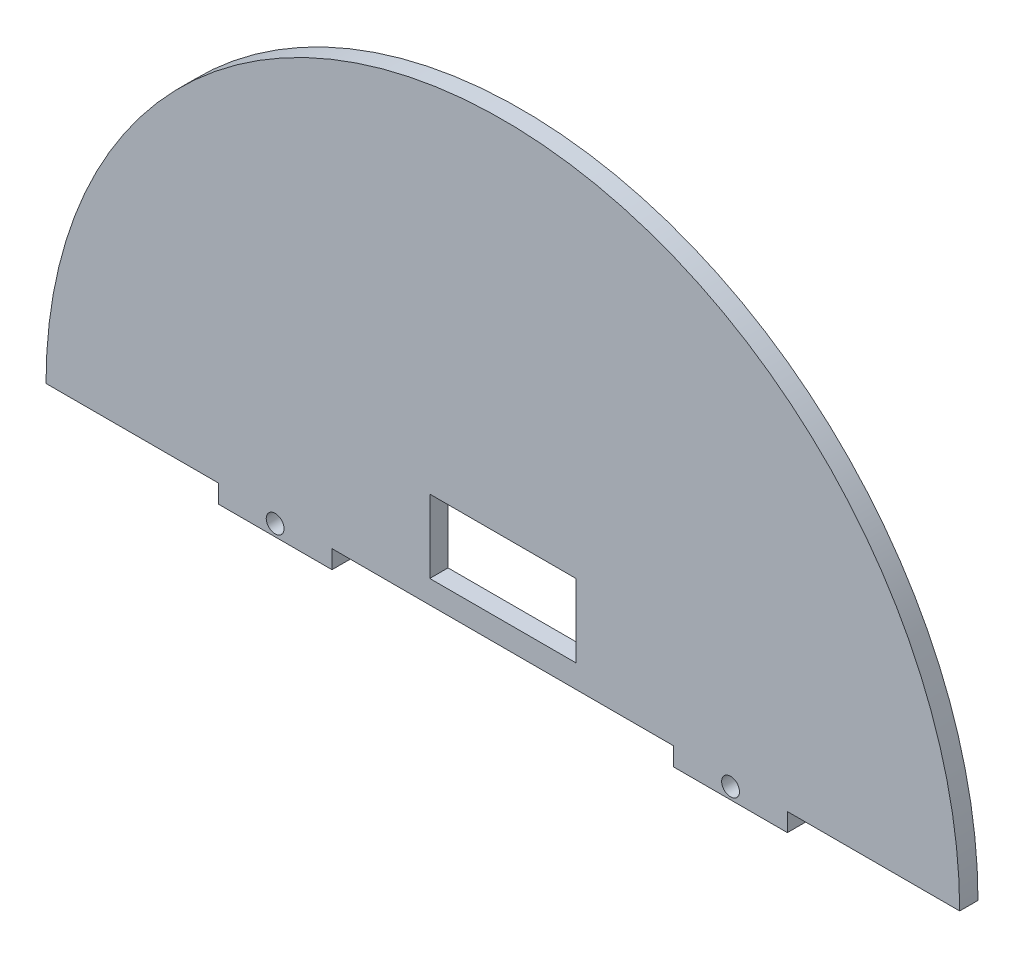
SolidWorks part; units mm, degrees
ref_plane "Front Plane" through (0, 0, 0) normal (0, 0, 1) x (1, 0, 0)
ref_plane "Top Plane" through (0, 0, 0) normal (0, 1, 0) x (1, 0, 0)
ref_plane "Right Plane" through (0, 0, 0) normal (1, 0, 0) x (0, 0, -1)
sketch "Sketch1" plane through (0, 0, 0) normal (0, 0, 1) x (1, 0, 0)
  line L0 (-79.38, 0) -> (79.38, 0)
  line L1 (0, 0) -> (0, 13.8053) construction
  line L2 (-49.44, 0) -> (-29.69, 0)
  line L3 (-49.44, 0) -> (-49.44, -3.18)
  line L4 (-49.44, -3.18) -> (-29.69, -3.18)
  line L5 (-29.69, 0) -> (-29.69, -3.18)
  line L6 (29.69, 0) -> (49.44, 0)
  line L7 (29.69, 0) -> (29.69, -3.18)
  line L8 (29.69, -3.18) -> (49.44, -3.18)
  line L9 (49.44, 0) -> (49.44, -3.18)
  line L11 (-12.7, 16.7) -> (12.7, 16.7)
  line L12 (-12.7, 16.7) -> (-12.7, 4)
  line L13 (-12.7, 4) -> (12.7, 4)
  line L14 (12.7, 16.7) -> (12.7, 4)
  line L15 (-12.7, 16.7) -> (12.7, 4) construction
  line L16 (-12.7, 4) -> (12.7, 16.7) construction
  arc A0 (79.38, 0) -> (-79.38, 0) centre (0, 0) ccw
  circle A1 centre (-39.565, -1.18) radius 1.55
  point P0 (-49.44, 0)
  point P4 (0, 0)
  point P10 (29.69, 0)
  point P16 (0, 10.35)
  dimension "D2" = 79.38
  dimension "D9" = 3.1
  dimension "D11" = 9.875
  dimension "D1" = 158.76
  dimension "D3" = 59.38
  dimension "D4" = 19.75
  dimension "D5" = 3.18
  dimension "D6" = 29.69
  dimension "D7" = 19.75
  dimension "D8" = 3.18
  dimension "D10" = 2
  dimension "D12" = 25.4
  dimension "D13" = 12.7
  dimension "D14" = 4
extrude "Boss-Extrude1" add sketch "Sketch1" along normal mid plane 3.18 contours L9 L0 L7 L8 | L0 A0 | L4 L5 L2 L3 region at (0.0021, 34.478, 0) region at (39.565, -1.59, 0)
extrude "Cut-Extrude2" cut sketch "Sketch1<4>" against normal mid plane 10 contours A1
sketch "Sketch1<4>" plane through (0, 0, 0) normal (0, 0, 1) x (1, 0, 0) same geometry as "Sketch1"
mirror "Mirror1" about plane through (0, 0, 0) normal (1, 0, 0) of "Cut-Extrude2"
